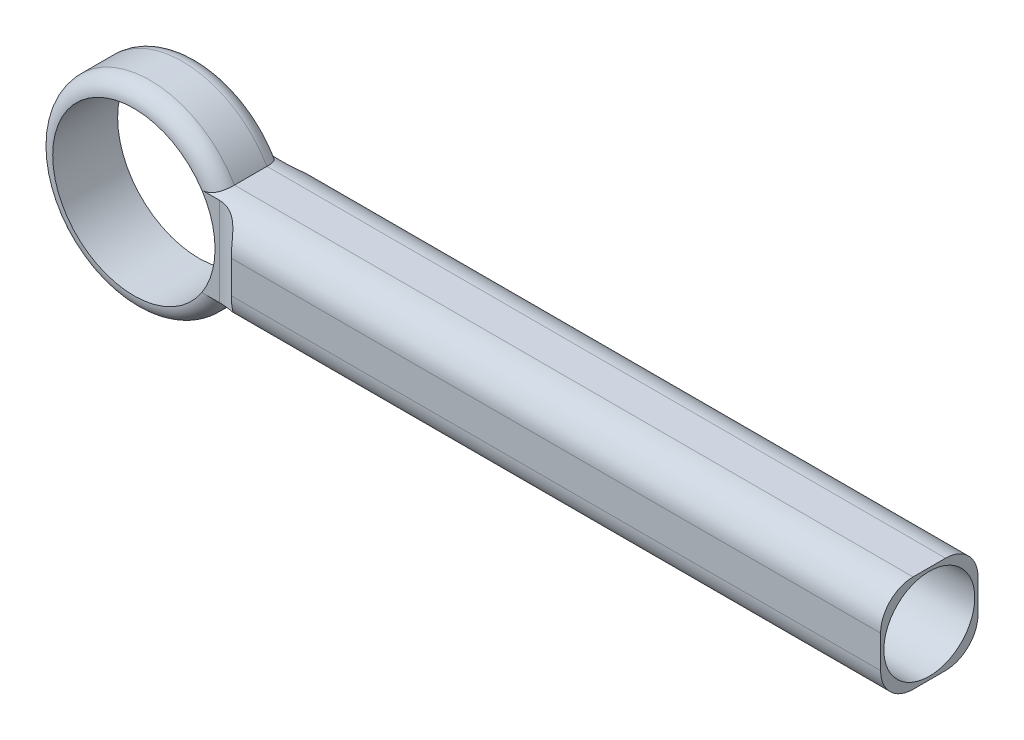
SolidWorks part; units mm, degrees
ref_plane "Plan de face" through (0, 0, 0) normal (0, 0, 1) x (1, 0, 0)
ref_plane "Plan de dessus" through (0, 0, 0) normal (0, 1, 0) x (1, 0, 0)
ref_plane "Plan de droite" through (0, 0, 0) normal (1, 0, 0) x (0, 0, -1)
sketch "Esquisse1" plane through (0, 0, 0) normal (0, 0, 1) x (1, 0, 0)
  line L0 (0, 0) -> (3.5, 0) construction
  line L2 (2.5981, 1.5) -> (3.5, 1.5)
  line L3 (3.5, 1.5) -> (3.5, -1.5)
  line L4 (3.5, -1.5) -> (2.5981, -1.5)
  arc A0 (2.5981, 1.5) -> (2.5981, -1.5) centre (0, 0) ccw
  circle A1 centre (0, 0) radius 2.5
  dimension "D1" = 5
  dimension "D2" = 6
  dimension "D3" = 3.5
  dimension "D4" = 3
extrude "Boss.-Extru.1" add sketch "Esquisse1" along normal blind 2
sketch "Esquisse2" plane through (3.5, 0, 0) normal (1, 0, 0) x (0, 0, -1)
  line L0 (0, 0) -> (-2, 0) construction
  line L2 (-2, -1.5) -> (-2, 1.5) construction
  line L8 (-2.5, -1.5) -> (0.5, -1.5)
  line L9 (-2.5, -1.5) -> (-2.5, 1.5)
  line L10 (-2.5, 1.5) -> (0.5, 1.5)
  line L11 (0.5, -1.5) -> (0.5, 1.5)
  line L12 (-2.5, -1.5) -> (0.5, 1.5) construction
  line L13 (-2.5, 1.5) -> (0.5, -1.5) construction
  point P6 (-1, 0)
  dimension "D1" = 3
  dimension "D2" = 3
extrude "Boss.-Extru.4" add sketch "Esquisse2" along normal blind 20 contours L9 L8 L11 L10
sketch "Esquisse3" plane through (23.5, 0, 0) normal (1, 0, 0) x (0, 0, -1)
  circle A0 centre (-1, 0) radius 1.4
  dimension "D1" = 2.8
extrude "Enlèv. mat.-Extru.2" cut sketch "Esquisse3" against normal blind 18
cosmetic thread "Représentation de filetage3" parameters "D2"=3.5
fillet "Congé1" radius 1 6 edges at (13.5, -1.5, 2.5) (13.5, -1.5, -0.5) (13.5, 1.5, -0.5) (13.5, 1.5, 2.5) (3.5, 0, 0) (3.5, 0, 2)
fillet "Congé2" radius 0.5 2 edges at (-3, 0, 2) (-3, 0, 0)
ref_plane "Plan1" through (0, 0, 1) normal (0, 0, 1) x (1, 0, 0)
sketch "Esquisse4" plane through (0, 0, 1) normal (0, 0, 1) x (1, 0, 0)
  circle A0 centre (0, 0) radius 2.5 construction
  arc A1 (2.0938, 1.366) -> (2.0938, -1.366) centre (0, 0) ccw construction
